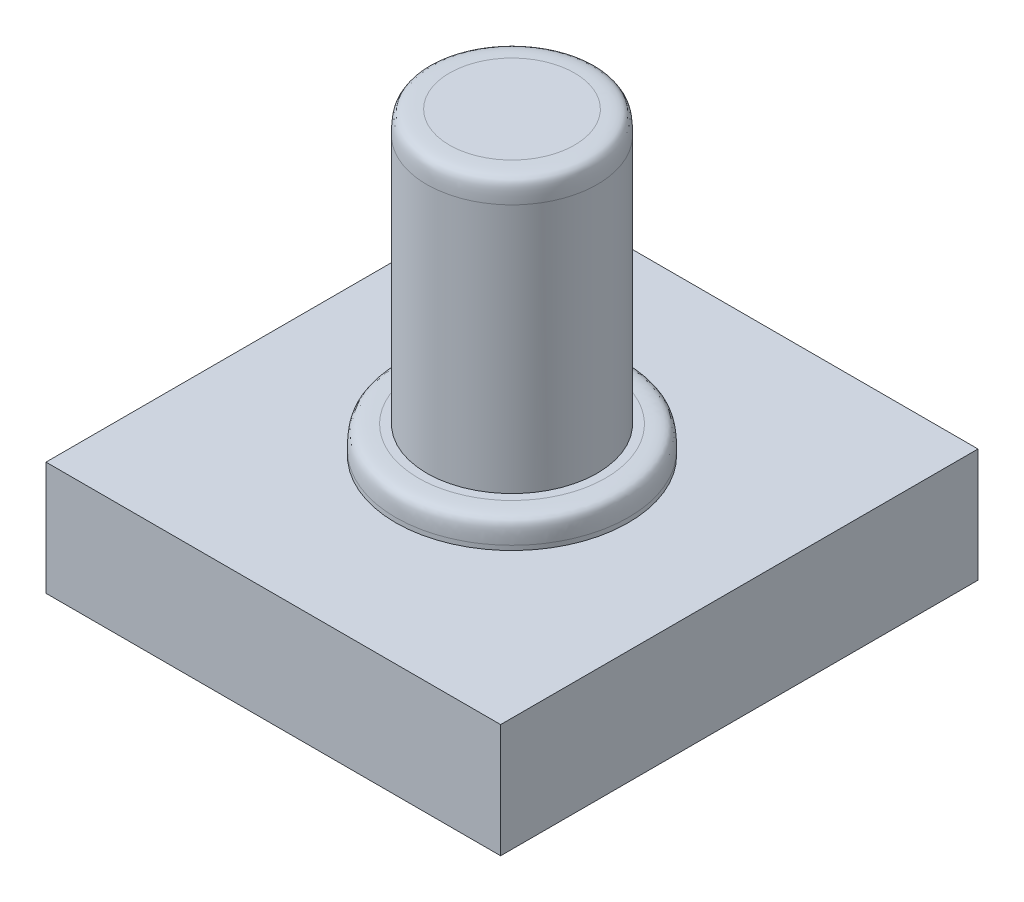
SolidWorks part; units mm, degrees
ref_plane "Спереди" through (0, 0, 0) normal (0, 0, 1) x (1, 0, 0)
ref_plane "Сверху" through (0, 0, 0) normal (0, 1, 0) x (1, 0, 0)
ref_plane "Справа" through (0, 0, 0) normal (1, 0, 0) x (0, 0, -1)
sketch "Эскиз2" plane through (0, 0, 0) normal (0, 1, 0) x (1, 0, 0)
  line L1 (-5, 5.25) -> (5, 5.25)
  line L2 (-5, 5.25) -> (-5, -5.25)
  line L3 (-5, -5.25) -> (5, -5.25)
  line L4 (5, 5.25) -> (5, -5.25)
  line L5 (-5, 5.25) -> (5, -5.25) construction
  line L6 (-5, -5.25) -> (5, 5.25) construction
  point P0 (0, 0)
  dimension "D1" = 10
  dimension "D2" = 10.5
extrude "Бобышка-Вытянуть1" add sketch "Эскиз2" along normal blind 2.5 contours L3 L4 L1 L2
sketch "Эскиз3" plane through (0, 2.5, 0) normal (0, 1, 0) x (1, 0, 0)
  circle A0 centre (0, 0) radius 2.56
  dimension "D1" = 5.12
extrude "Бобышка-Вытянуть2" add sketch "Эскиз3" along normal blind 0.6 contours A0
fillet "Скругление1" radius 0.5 1 edges at (0, 3.1, 2.56) conic rho 0.7
sketch "Эскиз4" plane through (0, 3.1, 0) normal (0, 1, 0) x (1, 0, 0)
  circle A0 centre (0, 0) radius 1.875
  dimension "D1" = 3.75
extrude "Бобышка-Вытянуть3" add sketch "Эскиз4" along normal blind 6 contours A0
fillet "Скругление2" radius 0.5 1 edges at (0, 9.1, 1.875) conic rho 0.7
